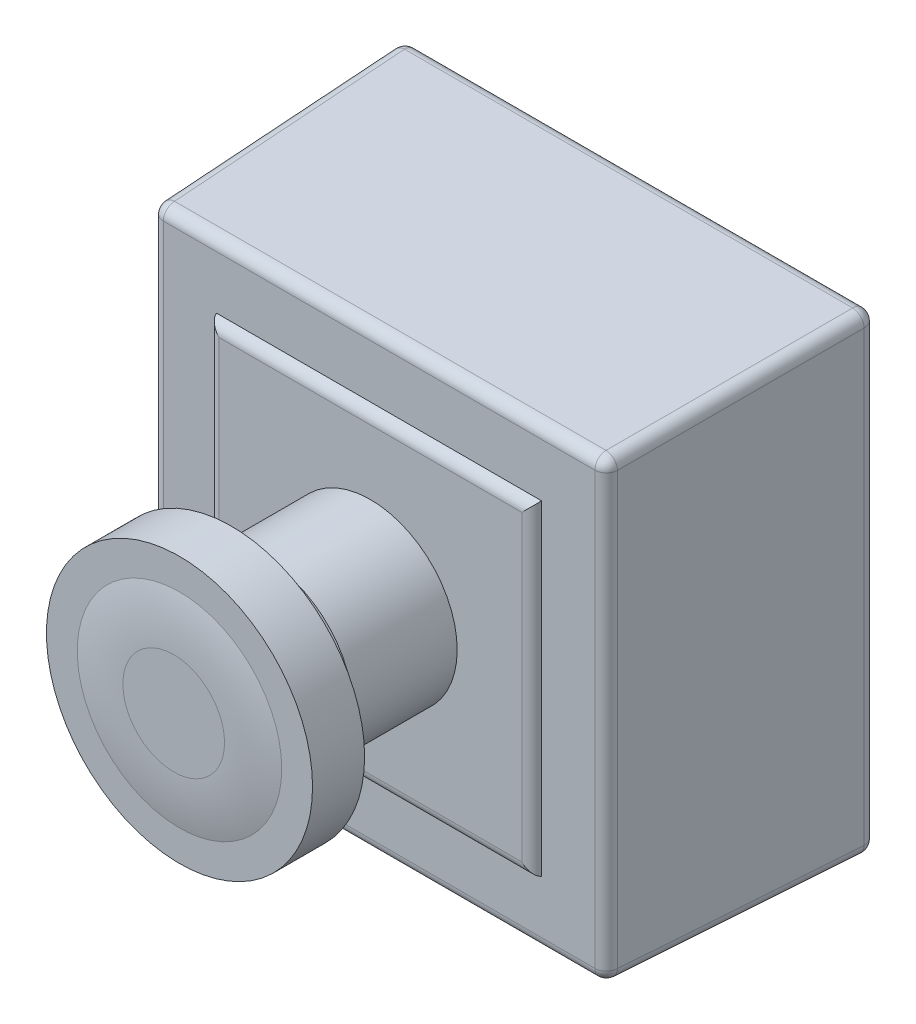
SolidWorks part; units mm, degrees
other "Marca1"
sketch "Croquis8" plane through (-20.3645, 20.3645, -5) normal (-0.7844, 0.6027, -0.1469) x (-0.3128, -0.1799, 0.9326)
ref_plane "Alzado" through (0, 0, 0) normal (0, 0, 1) x (1, 0, 0)
ref_plane "Planta" through (0, 0, 0) normal (0, 1, 0) x (1, 0, 0)
ref_plane "Vista lateral" through (0, 0, 0) normal (1, 0, 0) x (0, 0, -1)
sketch "Croquis1" plane through (0, 0, 0) normal (0, 0, 1) x (1, 0, 0)
  line L1 (-20.4, 20.4) -> (20.4, 20.4)
  line L2 (-20.4, 20.4) -> (-20.4, -20.4)
  line L3 (-20.4, -20.4) -> (20.4, -20.4)
  line L4 (20.4, 20.4) -> (20.4, -20.4)
  line L5 (-20.4, 20.4) -> (20.4, -20.4) construction
  line L6 (-20.4, -20.4) -> (20.4, 20.4) construction
  point P0 (0, 0)
  dimension "D1" = 40.8
extrude "Saliente-Extruir1" add sketch "Croquis1" along normal blind 22.6 draft 2
sketch "Croquis2" plane through (0, 0, 22.6) normal (0, 0, 1) x (1, 0, 0)
  line L1 (-14.05, 14.05) -> (14.05, 14.05)
  line L2 (-14.05, 14.05) -> (-14.05, -14.05)
  line L3 (-14.05, -14.05) -> (14.05, -14.05)
  line L4 (14.05, 14.05) -> (14.05, -14.05)
  line L5 (-14.05, 14.05) -> (14.05, -14.05) construction
  line L6 (-14.05, -14.05) -> (14.05, 14.05) construction
  point P0 (0, 0)
  dimension "D1" = 28.1
extrude "Saliente-Extruir2" add sketch "Croquis2" along normal mid plane 1.5
fillet "Redondeo1" radius 1 4 edges at (14.05, 0, 23.35) (0, 14.05, 23.35) (0, -14.05, 23.35) (-14.05, 0, 23.35)
sketch "Croquis3" plane through (0, 0, 23.35) normal (0, 0, 1) x (1, 0, 0)
  circle A0 centre (0, 0) radius 7.5
  dimension "D1" = 15
extrude "Saliente-Extruir3" add sketch "Croquis3" along normal blind 9
sketch "Croquis4" plane through (0, 0, 32.35) normal (0, 0, 1) x (1, 0, 0)
  circle A2 centre (0, 0) radius 5.8
  circle A3 centre (0, 0) radius 5.8
  dimension "D1" = 1.7
extrude "Saliente-Extruir4" add sketch "Croquis4" along normal blind 3
sketch "Croquis7" plane through (0, 0, 0) normal (0, 0, -1) x (-1, 0, 0)
  line L0 (-20.4, 20.4) -> (20.4, 20.4) construction
  line L1 (-20.4, -20.4) -> (-20.4, 20.4) construction
  circle A0 centre (-9.4, 11.9) radius 2.5
  dimension "D1" = 8.5
  dimension "D2" = 11
  dimension "D3" = 5
extrude "Saliente-Extruir7" add sketch "Croquis7" along normal blind 5
fillet "Redondeo5" radius 1 12 edges at (0, -19.6108, 22.6) (-19.6108, 0, 22.6) (0, 19.6108, 22.6) (19.6108, 0, 22.6) (-20.4, 0, 0) (0, 20.4, 0) (20.4, 0, 0) (0, -20.4, 0) (-20.0054, -20.0054, 11.3) (20.0054, -20.0054, 11.3) (20.0054, 20.0054, 11.3) (-20.0054, 20.0054, 11.3)
sketch "Croquis10" [suppressed] plane through (0, 0, 35.35) normal (0, 0, 1) x (1, 0, 0)
  circle A0 centre (0, 0) radius 7
  dimension "D1" = 14
extrude "Saliente-Extruir8" [suppressed] add sketch "Croquis10" along normal blind 5
sketch "Croquis11" [suppressed] plane through (0, 0, 40.35) normal (0, 0, 1) x (1, 0, 0)
  circle A2 centre (0, 0) radius 4.8
  circle A3 centre (0, 0) radius 4.8
  dimension "D1" = 2.2
extrude "Cortar-Extruir1" [suppressed] cut sketch "Croquis11" against normal blind 0.5
fillet "Redondeo6" [suppressed] radius 10
sketch "Croquis12" [suppressed] plane through (0, 0, 0) normal (0, 1, 0) x (1, 0, 0)
  circle A0 centre (0, -27.0153) radius 1
  dimension "D1" = 2
extrude "Saliente-Extruir9" [suppressed] add sketch "Croquis12" along normal blind 10
sketch "Croquis13" [suppressed] plane through (0, 10, 0) normal (0, 1, 0) x (1, 0, 0)
  circle A0 centre (0, -27.0153) radius 1.2565
extrude "Saliente-Extruir10" [suppressed] add sketch "Croquis13" along normal blind 0.5
fillet "Redondeo7" [suppressed] radius 0.3
sketch "Croquis14" [suppressed] plane through (0, 0, 35.35) normal (0, 0, 1) x (1, 0, 0)
  circle A0 centre (0, 0) radius 6.5
  dimension "D1" = 13
extrude "Saliente-Extruir11" [suppressed] add sketch "Croquis14" along normal blind 5
sketch "Croquis15" [suppressed] plane through (0, 0, 40.35) normal (0, 0, 1) x (1, 0, 0)
  circle A2 centre (0, 0) radius 4.3
  circle A3 centre (0, 0) radius 4.3
  dimension "D1" = 2.2
extrude "Cortar-Extruir2" [suppressed] cut sketch "Croquis15" against normal blind 1
fillet "Redondeo8" [suppressed] radius 5
sketch "Croquis16" plane through (0, 0, 35.35) normal (0, 0, 1) x (1, 0, 0)
  circle A0 centre (0, 0) radius 11.5
  dimension "D1" = 23
extrude "Saliente-Extruir12" add sketch "Croquis16" along normal blind 4.5
sketch "Croquis17" plane through (0, 0, 39.85) normal (0, 0, 1) x (1, 0, 0)
  circle A0 centre (0, 0) radius 8.8361
extrude "Saliente-Extruir13" add sketch "Croquis17" along normal blind 0.5
fillet "Redondeo9" radius 20 1 edges at (8.8361, 0, 40.35)
sketch "Sketch1" plane through (0, 0, 0) normal (1, 0, 0) x (0, 0, -1)
  line L0 (0, 0) -> (-22.6, 0) construction
  line L1 (-22.6, 14.05) -> (-22.6, -14.05) construction
  line L2 (-23.35, -20) -> (-23.35, 20) construction
  line L3 (-23.35, 20) -> (0.15, 20.8) construction
  line L4 (0.15, 20.8) -> (0.15, -20.8) construction
  line L5 (0.15, -20.8) -> (-23.35, -20) construction
  line L6 (-23.35, 7.5) -> (-23.35, -7.5) construction
  point P5 (-23.35, 0)
  point P8 (-23.35, 0)
  dimension "D1" = 40
  dimension "D2" = 41.6
  dimension "D3" = 23.5
